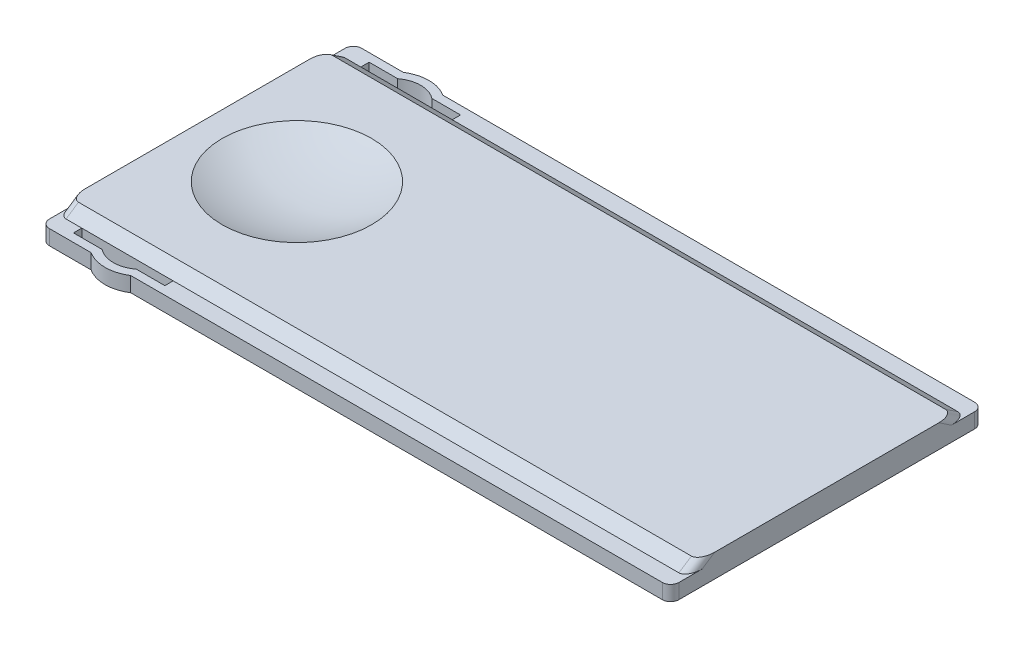
SolidWorks part; units mm, degrees
ref_plane "Front Plane" through (0, 0, 0) normal (0, 0, 1) x (1, 0, 0)
ref_plane "Top Plane" through (0, 0, 0) normal (0, 1, 0) x (1, 0, 0)
ref_plane "Right Plane" through (0, 0, 0) normal (1, 0, 0) x (0, 0, -1)
sketch "Sketch1" plane through (0, 0, 0) normal (1, 0, 0) x (0, 0, -1)
  line L0 (18.8, 0) -> (-18.8, 0)
  line L1 (-18.8, 0) -> (-18.8, 1.8)
  line L2 (-18.8, 1.8) -> (-16.8, 1.8)
  line L3 (-16.8, 1.8) -> (-15.3, 2.8)
  line L4 (-15.3, 2.8) -> (15.3, 2.8)
  line L5 (0, 2.8) -> (0, 0) construction
  line L6 (16.8, 1.8) -> (15.3, 2.8)
  line L7 (18.8, 1.8) -> (16.8, 1.8)
  line L8 (18.8, 0) -> (18.8, 1.8)
  dimension "D1" = 1.8
  dimension "D2" = 37.6
  dimension "D3" = 2.8
  dimension "D4" = 2
  dimension "D5" = 1.5
extrude "Boss-Extrude1" add sketch "Sketch1" along normal blind 75.8
sketch "Sketch2" plane through (0, 1.8, 0) normal (0, 1, 0) x (1, 0, 0)
  line L0 (0, 0) -> (75.8, 0) construction
  line L1 (75.8, 15.3) -> (75.8, -15.3) construction
  line L3 (0, 15.3) -> (0, -15.3) construction
  circle A0 centre (8.4, 15.1) radius 4.4
  circle A1 centre (8.4, -15.1) radius 4.4
  dimension "D1" = 8.8
  dimension "D2" = 15.1
  dimension "D3" = 8.4
extrude "Boss-Extrude-Latch" add sketch "Sketch2" against normal up to surface (1.8 mm away) up to face at (37.9, 0, 0)
sketch "Sketch3" plane through (0, 1.8, 0) normal (0, 1, 0) x (1, 0, 0)
  line L1 (2.9, 17.8) -> (6.3336, 17.8)
  line L2 (2.9, 17.8) -> (2.9, 16.8)
  line L3 (2.9, 16.8) -> (13.9, 16.8)
  line L4 (13.9, 17.8) -> (13.9, 16.8)
  line L5 (2.9, 17.8) -> (13.9, 16.8) construction
  line L6 (2.9, 16.8) -> (13.9, 17.8) construction
  line L7 (8.4, 19.5) -> (8.4, 17.3) construction
  line L9 (0, 18.8) -> (0, 16.8) construction
  line L10 (75.8, 16.8) -> (0, 16.8) construction
  line L11 (0, 0) -> (75.8, 0) construction
  line L12 (75.8, 15.3) -> (75.8, -15.3) construction
  line L13 (13.9, -17.8) -> (13.9, -16.8)
  line L14 (10.4664, -17.8) -> (13.9, -17.8)
  line L15 (2.9, -17.8) -> (6.3336, -17.8)
  line L16 (2.9, -17.8) -> (2.9, -16.8)
  line L17 (10.4664, 17.8) -> (13.9, 17.8)
  line L18 (6.0188, 18.8) -> (0, 18.8) construction
  line L19 (2.9, -16.8) -> (13.9, -16.8)
  arc A0 (10.7812, 18.8) -> (6.0188, 18.8) centre (8.4, 15.1) ccw construction
  arc A2 (10.4664, -17.8) -> (6.3336, -17.8) centre (8.4, -15.1) cw
  arc A3 (10.24, 17.9591) -> (6.56, 17.9591) centre (8.4, 15.1) ccw
  arc A4 (10.4664, 17.8) -> (6.3336, 17.8) centre (8.4, 15.1) ccw
  point P0 (8.4, 17.3)
  dimension "D5" = 1
  dimension "D1" = 1
  dimension "D2" = 1
  dimension "D3" = 11
  dimension "D4" = 2.9
extrude "Cut-Extrude1" cut sketch "Sketch3" against normal through all
sketch "Sketch4" plane through (0, 0, 0) normal (0, 0, 1) x (1, 0, 0)
  line L0 (12, 43.3) -> (12, 0.8)
  line L2 (3, 2.8) -> (12, 2.8) construction
  line L3 (75.8, 2.8) -> (0, 2.8) construction
  arc A0 (12, 0.8) -> (12, 43.3) centre (12, 22.05) cw
  dimension "D1" = 0.8
  dimension "D2" = 9
  dimension "D3" = 12
revolve "Cut-Revolve1" cut sketch "Sketch4" angle 360 about L0
fillet "Fillet1" radius 1 8 edges at (75.8, 0.9, 18.8) (75.8, 2.3, 16.05) (75.8, 2.3, -16.05) (75.8, 0.9, -18.8) (0, 0.9, 18.8) (0, 2.3, 16.05) (0, 2.3, -16.05) (0, 0.9, -18.8)
